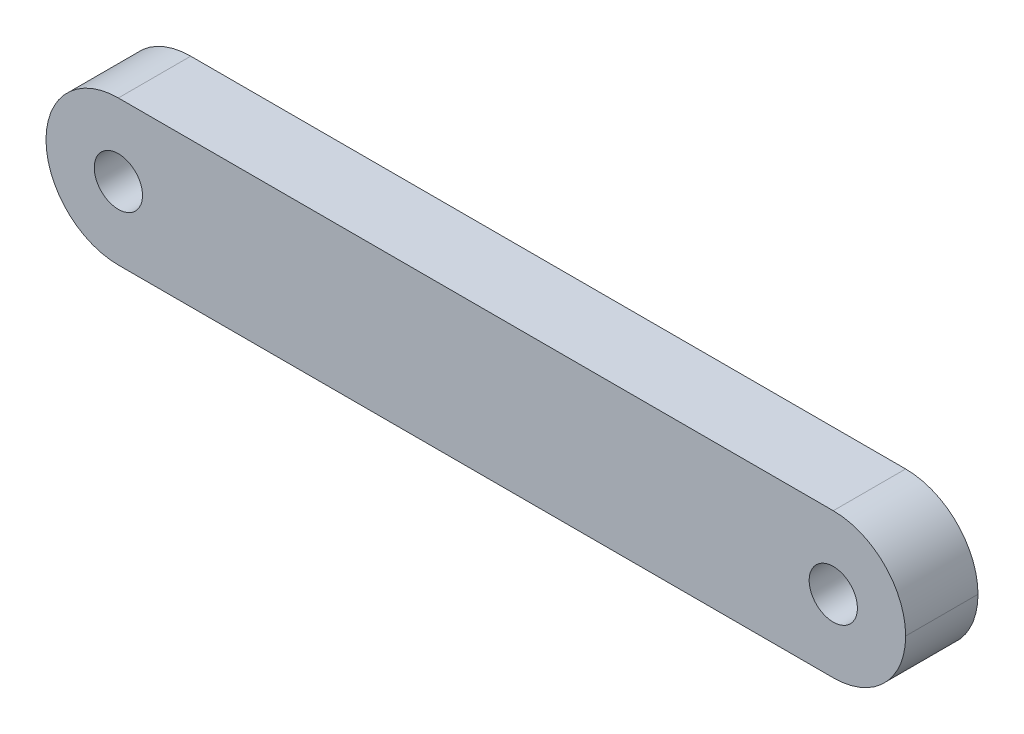
SolidWorks part; units mm, degrees
ref_plane "Front" through (0, 0, 0) normal (0, 0, 1) x (1, 0, 0)
ref_plane "Top" through (0, 0, 0) normal (0, 1, 0) x (1, 0, 0)
ref_plane "Right" through (0, 0, 0) normal (1, 0, 0) x (0, 0, -1)
sketch "Sketch1" plane through (0, 0, 0) normal (0, 0, 1) x (1, 0, 0)
  line L0 (0, 3) -> (35.64, 3) construction
  line L1 (0, 0) -> (35.64, 0)
  line L2 (0, 0) -> (0, 6)
  line L3 (0, 6) -> (35.64, 6)
  line L4 (35.64, 0) -> (35.64, 6)
  circle A0 centre (3, 3) radius 1
  circle A1 centre (32.64, 3) radius 1
  dimension "D1" = 2
  dimension "D2" = 2
  dimension "D3" = 2
  dimension "D4" = 2
  dimension "D5" = 29.64
  dimension "D6" = 6
extrude "Boss-Extrude1" add sketch "Sketch1" along normal blind 3
fillet "Fillet1" radius 3 4 edges at (35.64, 0, 1.5) (35.64, 6, 1.5) (0, 0, 1.5) (0, 6, 1.5)
